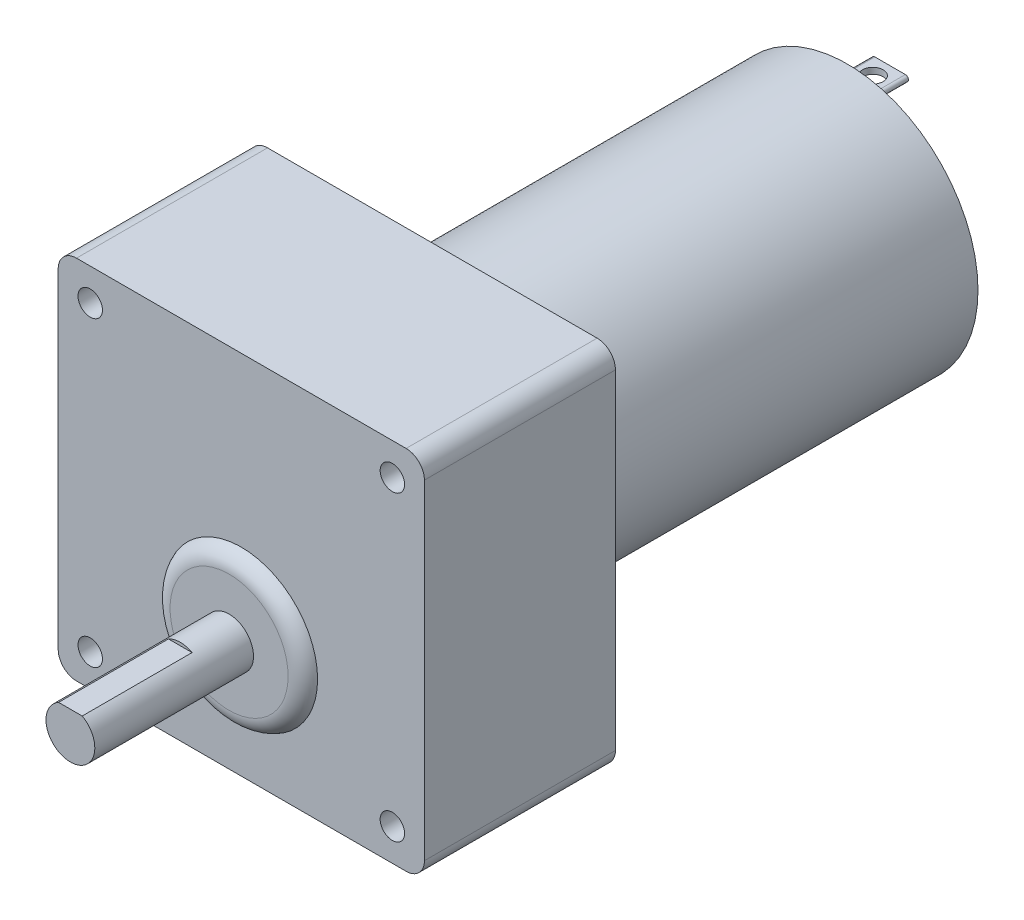
SolidWorks part; units mm, degrees
ref_plane "Front Plane" through (0, 0, 0) normal (0, 0, 1) x (1, 0, 0)
ref_plane "Top Plane" through (0, 0, 0) normal (0, 1, 0) x (1, 0, 0)
ref_plane "Right Plane" through (0, 0, 0) normal (1, 0, 0) x (0, 0, -1)
sketch "Sketch1" plane through (0, 0, 0) normal (0, 0, 1) x (1, 0, 0)
  circle A0 centre (0, 0) radius 21.4
  dimension "D1" = 42.8
extrude "Boss-Extrude1" add sketch "Sketch1" along normal blind 68
sketch "Sketch2" plane through (0, 0, 68) normal (0, 0, 1) x (1, 0, 0)
  line L0 (-30, 0) -> (30, 0) construction
  line L1 (-30, 30) -> (30, 30)
  line L2 (-30, 30) -> (-30, -30)
  line L3 (-30, -30) -> (30, -30)
  line L4 (30, 30) -> (30, -30)
  line L5 (-30, 30) -> (30, -30) construction
  line L6 (-30, -30) -> (30, 30) construction
  circle A0 centre (-24.75, 24.75) radius 2
  circle A1 centre (24.75, 24.75) radius 2
  circle A2 centre (24.75, -24.75) radius 2
  circle A3 centre (-24.75, -24.75) radius 2
  point P0 (0, 0)
  dimension "D3" = 4
  dimension "D1" = 60
  dimension "D2" = 60
  dimension "D4" = 49.5
extrude "Boss-Extrude2" add sketch "Sketch2" along normal blind 31.3
sketch "Sketch3" plane through (0, 0, 99.3) normal (0, 0, 1) x (1, 0, 0)
  circle A0 centre (0, -10) radius 12.5
  dimension "D1" = 25
  dimension "D2" = 10
extrude "Boss-Extrude3" add sketch "Sketch3" along normal blind 2
fillet "Fillet1" radius 3 1 edges at (12.5, -10, 101.3)
sketch "Sketch4" plane through (0, 0, 101.3) normal (0, 0, 1) x (1, 0, 0)
  circle A0 centre (0, -10) radius 4
  dimension "D1" = 8
extrude "Boss-Extrude4" add sketch "Sketch4" along normal blind 8
sketch "Sketch5" plane through (0, 0, 109.3) normal (0, 0, 1) x (1, 0, 0)
  line L0 (-1.9365, -6.5) -> (1.9365, -6.5)
  circle A1 centre (0, -10) radius 4
  circle A2 centre (0, -10) radius 4
  circle M3 centre (0, -10) radius 4
  dimension "D2" = 3.5
  dimension "D1" = 0
extrude "Boss-Extrude5" add sketch "Sketch5" along normal blind 18 contours L0 M3 region at (0, -10.0989, 109.3)
fillet "Fillet2" radius 3 4 edges at (-30, 30, 83.65) (-30, -30, 83.65) (30, -30, 83.65) (30, 30, 83.65)
sketch "Sketch6" plane through (0, 0, 0) normal (0, 0, -1) x (-1, 0, 0)
  line L0 (-2.5, 17.15) -> (2.5, 17.15) construction
  line L1 (-2.5, 17.65) -> (2.5, 17.65)
  line L2 (-2.5, 16.65) -> (2.5, 16.65)
  line L3 (-21.4, 0) -> (21.4, 0) construction
  line L4 (-2.5, -17.15) -> (2.5, -17.15) construction
  line L5 (-2.5, -17.65) -> (2.5, -17.65)
  line L6 (-2.5, -16.65) -> (2.5, -16.65)
  arc A0 (-2.5, 17.65) -> (-2.5, 16.65) centre (-2.5, 17.15) ccw
  arc A1 (2.5, 16.65) -> (2.5, 17.65) centre (2.5, 17.15) ccw
  circle A2 centre (0, 0) radius 21.4 construction
  circle A3 centre (0, 0) radius 21.4 construction
  arc A4 (-2.5, -17.65) -> (-2.5, -16.65) centre (-2.5, -17.15) cw
  arc A5 (2.5, -16.65) -> (2.5, -17.65) centre (2.5, -17.15) cw
  point P2 (0, 17.15)
  point P17 (0, -17.15)
  dimension "D1" = 1
  dimension "D2" = 5
  dimension "D3" = 17.15
extrude "Boss-Extrude6" add sketch "Sketch6" along normal blind 7
sketch "Sketch7" plane through (0, 17.65, 0) normal (0, 1, 0) x (1, 0, 0)
  circle A0 centre (0, 4.1763) radius 1.6863
extrude "Cut-Extrude1" cut sketch "Sketch7" against normal up to surface (35.3 mm away) up to face at (0, -17.65, -3.5)
